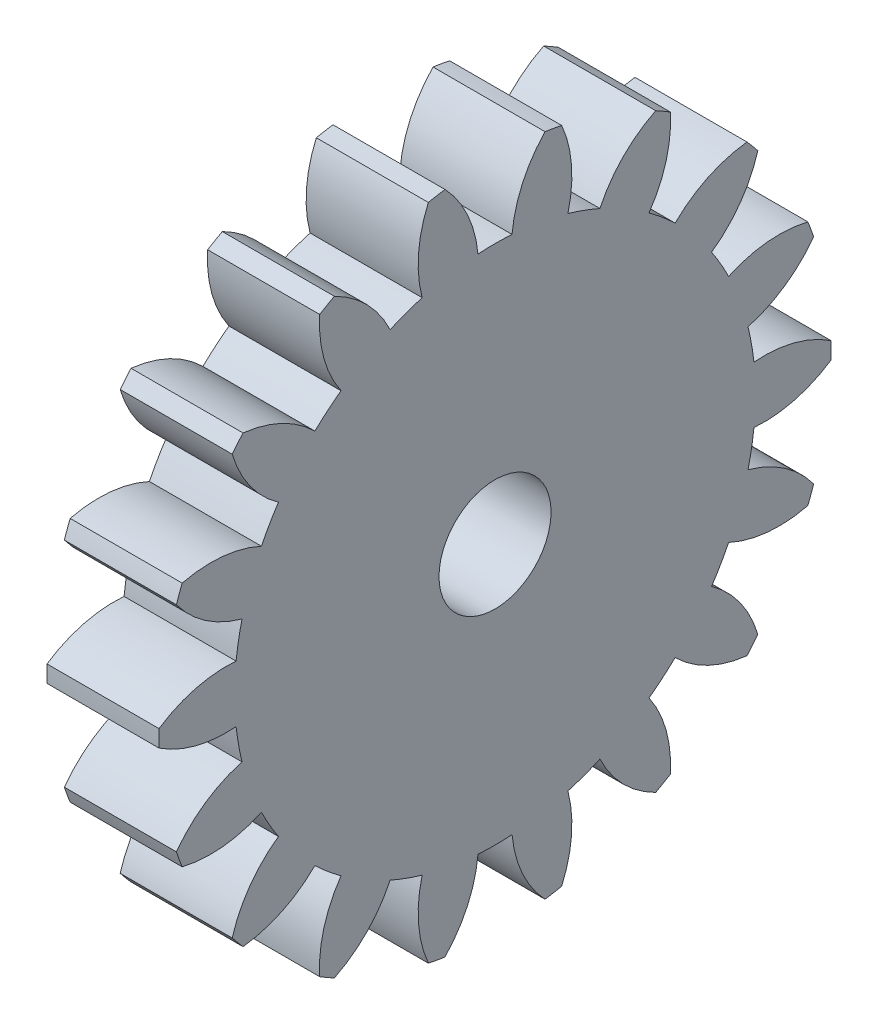
SolidWorks part; units mm, degrees
ref_plane "Plane1" through (0, 0, 0) normal (0, 0, 1) x (1, 0, 0)
ref_plane "Plane2" through (0, 0, 0) normal (0, 1, 0) x (1, 0, 0)
ref_plane "Plane3" through (0, 0, 0) normal (1, 0, 0) x (0, 0, -1)
sketch "HoldingSke" plane through (0, 0, 0) normal (0, 1, 0) x (1, 0, 0)
  line L0 (0, 0) -> (0.634, -0.206)
  line L1 (-15, 0) -> (100, 0) construction
  line L2 (0, 0) -> (-2.1039, 2.3779)
  line L3 (0, 0) -> (-11.863, 4.5341)
  line L4 (0, 0) -> (8.2133, 2.6687)
  line L5 (0, 0) -> (-46.8476, -17.4728)
  line L6 (0, 0) -> (-4.1448, -2.7965)
  line L7 (-2.1039, 2.3779) -> (8.6586, 51.2059)
  line L8 (-76.2, 54.61) -> (-75.3, 54.61)
  line L9 (-71.009, 38.7566) -> (-53.1078, 45.2721)
  line L10 (-76.2, 71.12) -> (104.1128, 71.12)
  line L11 (0, 0) -> (-5, 0)
  line L12 (-76.2, 101.6) -> (-76.147, 101.6)
  line L13 (24.9733, 27.94) -> (52.9518, 28.4284)
  line L14 (24.9733, 27.94) -> (24.9743, 27.94)
  line L15 (24.9733, 27.94) -> (100.4006, 29.5858)
  line L16 (-63.627, -1.5) -> (-12.827, -1.5)
  circle A0 centre (0, 0) radius 2.5
  circle A1 centre (0, 0) radius 11.624
  circle A2 centre (0, 0) radius 37.5
  circle A3 centre (0, 0) radius 2.5
  dimension "Num_teeth" = 18
  dimension "Pitch_radius" = 180.3128
  dimension "Width" = 5
  dimension "Thickness" = 5
sketch "BasProSke" plane through (0, 0, 0) normal (0, 1, 0) x (1, 0, 0)
  line L0 (-10, 0) -> (60, 0) construction
  line L1 (0, 0) -> (0, 15)
  line L2 (0, 0) -> (5, 0)
  line L3 (5, 0) -> (5, 15)
  line L4 (5, 15) -> (0, 15)
  dimension "Thickness" = 5
  dimension "Diameter" = 30
revolve "Base-Revolve" add sketch "BasProSke" angle 360 about L0
sketch "TooCutSke" plane through (0, 0, 0) normal (1, 0, 0) x (0, 0, -1)
  line L1 (0, 0) -> (0, 107) construction
  line L2 (0, 0) -> (-1.2693, 13.4402) construction
  line L3 (0, 0) -> (-4.6734, 26.504) construction
  line L4 (-1.2693, 13.4402) -> (-2.3367, 13.252) construction
  arc A0 (0.76, 11.5991) -> (-0.76, 11.5991) centre (0, 0) ccw
  arc A1 (2.2542, 14.8553) -> (-2.2542, 14.8553) centre (0, 0) ccw
  circle A2 centre (0, 0) radius 13.5 construction
  circle A3 centre (0, 0) radius 12.6859 construction
  arc A4 (-0.76, 11.5991) -> (-2.2542, 14.8553) centre (-6.1371, 11.1026) ccw
  arc A5 (2.2542, 14.8553) -> (0.76, 11.5991) centre (6.1371, 11.1026) ccw
extrude "ToothCut" cut sketch "TooCutSke" along normal through all
fillet "Breaks" [suppressed] radius 0.03 tangent propagation no
fillet "RootFillets" [suppressed] radius 0.376
pattern_circular "TeethCuts" count 18 every 20 about axis through (-10, 0, 0) along (1, 0, 0) of "ToothCut", "RootFillets", "Breaks"
sketch "HubNeaOneSke" plane through (0, 0, 0) normal (-1, 0, 0) x (0, 0, 1)
  circle A0 centre (0, 0) radius 11.624
  dimension "Diameter" = 23.248
extrude "HubNearOne" [suppressed] add sketch "HubNeaOneSke" along normal blind 45.0001
sketch "HubNeaBotSke" plane through (0, 0, 0) normal (-1, 0, 0) x (0, 0, 1)
  circle A0 centre (0, 0) radius 11.624
  dimension "Diameter" = 23.248
extrude "HubNearBoth" [suppressed] add sketch "HubNeaBotSke" along normal blind 22.5
ref_plane "FarPln" through (5, 0, 0) normal (1, 0, 0) x (0, 0, -1)
sketch "HubFarSke" plane through (5, 0, 0) normal (1, 0, 0) x (0, 0, -1)
  circle A0 centre (0, 0) radius 11.624
  dimension "Diameter" = 23.248
extrude "HubFar" [suppressed] add sketch "HubFarSke" along normal blind 22.5
sketch "BorSke" plane through (0, 0, 0) normal (1, 0, 0) x (0, 0, -1)
  circle A0 centre (0, 0) radius 2.5
  dimension "Diameter" = 5
extrude "Bore" cut sketch "BorSke" along normal mid plane 100.0001
sketch "KeySke" plane through (0, 0, 0) normal (1, 0, 0) x (0, 0, -1)
  line L0 (-1, 0) -> (-1, 3.4)
  line L1 (-1, 3.4) -> (1, 3.4)
  line L2 (1, 3.4) -> (1, 0)
  line L3 (0, 0) -> (0, 34) construction
  line L4 (-1, 0) -> (1, 0)
  dimension "Width" = 2
extrude "Keyway" [suppressed] cut sketch "KeySke" along normal mid plane 100.0001
pattern_circular "Keyway2" [suppressed] count 2 every 90 about axis through (-10, 0, 0) along (1, 0, 0) reverse direction yes
equation "' \"Module@HoldingSke\" = 6.35"
equation "' \"Num_teeth@HoldingSke\" = 12"
equation "' \"Ap@HoldingSke\" =  20"
equation "' \"Ap@HoldingSke\" = 20"
equation "' \"Width@HoldingSke\" = 0.5 * 25.4"
equation "' \"Hub_dia@HoldingSke\"= 1 * 25.4"
equation "' \"Hub_dia@HoldingSke\" = 1 * 25.4"
equation "' \"Overall_len@HoldingSke\" = 1.0 * 25.4"
equation "' \"Bore@HoldingSke\" = 0.75 * 25.4"
equation "' \"T_dim@HoldingSke\" = 0.1 * 25.4"
equation "' \"Width@KeySke\" = 0.25 * 25.4"
equation "' \"Show_teeth@HoldingSke\" = 13"
equation "' \"Backlash@HoldingSke\" = 0.009 * 25.4"
equation "' \"Addendum_fac@HoldingSke\" = 1.0"
equation "' \"Dedendum_fac@HoldingSke\" = 1.25"
equation "' \"Dedendum_add@HoldingSke\" = 0.00005 * 25.4"
equation "' \"Clearance_fac@HoldingSke\" = 0.25"
equation "\"Pitch@HoldingSke\" = 1 / \"Module@HoldingSke\""
equation "\"Overcut_dia@TooCutSke\" = (\"Num_teeth@HoldingSke\" + 2 * \"Addendum_fac@HoldingSke\") / \"Pitch@HoldingSke\" + 0.002 * 25.4"
equation "\"Pitch_dia@TooCutSke\" = \"Num_teeth@HoldingSke\" / \"Pitch@HoldingSke\""
equation "\"Base_dia@TooCutSke\" = \"Num_teeth@HoldingSke\" / \"Pitch@HoldingSke\" * cos((\"Ap@HoldingSke\"  * 3.14159265 / 180))"
equation "\"Root_dia@TooCutSke\" = (\"Num_teeth@HoldingSke\" + 2) / \"Pitch@HoldingSke\" - 2 * (\"Addendum_fac@HoldingSke\" + \"Dedendum_fac@HoldingSke\") / \"Pitch@HoldingSke\" - \"Dedendum_add@HoldingSke\" * 2"
equation "\"Half_ang@TooCutSke\" = 180 / \"Num_teeth@HoldingSke\""
equation "\"Half_CT@TooCutSke\" = \"Num_teeth@HoldingSke\" / \"Pitch@HoldingSke\" * sin((3.14159265 / 2 / \"Num_teeth@HoldingSke\")) / 2 - 7 * \"Backlash@HoldingSke\" / 4"
equation "\"Flank_rad@TooCutSke\" = \"Num_teeth@HoldingSke\" / \"Pitch@HoldingSke\" / 5"
equation "\"Radius@RootFillets\" = \"Clearance_fac@HoldingSke\" / \"Pitch@HoldingSke\" + \"Dedendum_add@HoldingSke\""
equation "\"Break_rad@Breaks\" = 0.02 / \"Pitch@HoldingSke\""
equation "\"Thickness@HoldingSke\" = \"Width@HoldingSke\""
equation "\"OAL@HoldingSke\" = \"Thickness@HoldingSke\""
equation "\"MHD@HoldingSke\" = (\"Num_teeth@HoldingSke\" + 2) / \"Pitch@HoldingSke\" - 2 * (\"Addendum_fac@HoldingSke\" + \"Dedendum_fac@HoldingSke\")  / \"Pitch@HoldingSke\" - \"Dedendum_add@HoldingSke\" * 2"
equation "\"MBD@HoldingSke\" = (\"Num_teeth@HoldingSke\" + 2) / \"Pitch@HoldingSke\" - 2 * (\"Addendum_fac@HoldingSke\" + \"Dedendum_fac@HoldingSke\")  / \"Pitch@HoldingSke\" - \"Dedendum_add@HoldingSke\" * 2 - 0.002 * 25.4"
equation "\"MHD@HoldingSke\" = ((sgn( \"MHD@HoldingSke\" - \"Hub_dia@HoldingSke\" )-1)*( \"MHD@HoldingSke\" - \"Hub_dia@HoldingSke\" ))/-2+ \"Hub_dia@HoldingSke\""
equation "\"MBD@HoldingSke\" = ((sgn( \"MBD@HoldingSke\" - \"Bore@HoldingSke\" )-1)*( \"MBD@HoldingSke\" - \"Bore@HoldingSke\" ))/-2+ \"Bore@HoldingSke\""
equation "\"OAL@HoldingSke\" = ((sgn( \"OAL@HoldingSke\" - \"Overall_len@HoldingSke\" )+1)*( \"OAL@HoldingSke\" - \"Overall_len@HoldingSke\" ))/2 + \"Overall_len@HoldingSke\" + 0.000002 * 25.4"
equation "\"Num_teeth@TeethCuts\" = int( \"Show_teeth@HoldingSke\" ) + 1"
equation "\"Num_teeth@TeethCuts\" = ((sgn( \"Num_teeth@TeethCuts\" - \"Num_teeth@HoldingSke\" )-1)*( \"Num_teeth@TeethCuts\" - \"Num_teeth@HoldingSke\" ))/-2+ \"Num_teeth@HoldingSke\""
equation "\"Num_teeth@TeethCuts\" = ((sgn( \"Num_teeth@TeethCuts\" - 2.0)+1)*( \"Num_teeth@TeethCuts\" - 2.0))/2 +2.0"
equation "\"Angle@TeethCuts\" = 360.0 / \"Num_teeth@HoldingSke\""
equation "\"Diameter@BasProSke\" = (\"Num_teeth@HoldingSke\" + 2 * \"Addendum_fac@HoldingSke\") / \"Pitch@HoldingSke\""
equation "\"Thickness@BasProSke\"  = \"Thickness@HoldingSke\""
equation "' \"Fillet_rad@BasProSke\" =  \"Thickness@HoldingSke\" * 0.05"
equation "' \"Fillet_rad@BasProSke\" = \"Thickness@HoldingSke\" * 0.05"
equation "\"MHD@HoldingSke\" = ((sgn( \"MHD@HoldingSke\" - \"Root_dia@TooCutSke\" )-1)*( \"MHD@HoldingSke\" - \"Root_dia@TooCutSke\" ))/-2+ \"Root_dia@TooCutSke\""
equation "\"Diameter@HubNeaOneSke\" = \"MHD@HoldingSke\""
equation "\"Length@HubNearOne\" = \"OAL@HoldingSke\" - \"Thickness@BasProSke\""
equation "\"Diameter@HubNeaBotSke\" = \"MHD@HoldingSke\""
equation "\"Length@HubNearBoth\" = ( \"OAL@HoldingSke\" - \"Thickness@BasProSke\" ) / 2.0"
equation "\"Thickness@FarPln\" = \"Thickness@BasProSke\""
equation "\"Diameter@HubFarSke\" = \"MHD@HoldingSke\""
equation "\"Length@HubFar\" = ( \"OAL@HoldingSke\" - \"Thickness@BasProSke\" ) / 2.0"
equation "\"Diameter@BorSke\" = \"MBD@HoldingSke\""
equation "\"D1@Bore\" = \"OAL@HoldingSke\" * 2.0"
equation "\"D1@Keyway\" = \"OAL@HoldingSke\" * 2.0"
equation "\"Offset@KeySke\" = \"T_dim@HoldingSke\" + \"MBD@HoldingSke\" / 2.0"
